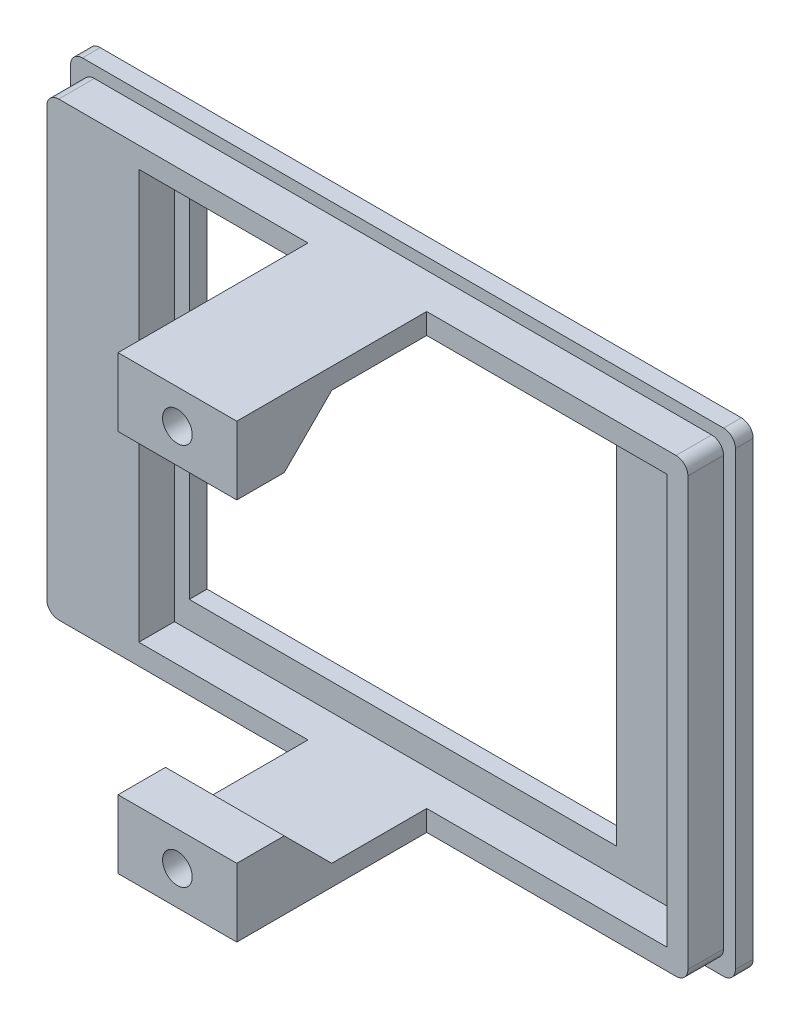
SolidWorks part; units mm, degrees
ref_plane "Front Plane" through (0, 0, 0) normal (0, 0, 1) x (1, 0, 0)
ref_plane "Top Plane" through (0, 0, 0) normal (0, 1, 0) x (1, 0, 0)
ref_plane "Right Plane" through (0, 0, 0) normal (1, 0, 0) x (0, 0, -1)
sketch "Sketch1" plane through (0, 0, 0) normal (0, 0, 1) x (1, 0, 0)
  line L1 (28, -20) -> (-28, -20)
  line L2 (28, -20) -> (28, 20)
  line L3 (28, 20) -> (-28, 20)
  line L4 (-28, -20) -> (-28, 20)
  line L5 (28, -20) -> (-28, 20) construction
  line L6 (28, 20) -> (-28, -20) construction
  line L7 (18, -15) -> (-18, -15)
  line L8 (18, -15) -> (18, 15)
  line L9 (18, 15) -> (-18, 15)
  line L10 (-18, -15) -> (-18, 15)
  line L11 (18, -15) -> (-18, 15) construction
  line L12 (18, 15) -> (-18, -15) construction
  point P0 (0, 0)
  point P6 (0, 0)
  dimension "D1" = 40
  dimension "D2" = 56
  dimension "D3" = 30
  dimension "D4" = 36
extrude "Boss-Extrude1" add sketch "Sketch1" along normal blind 1.5
sketch "Sketch2" plane through (0, 0, 1.5) normal (0, 0, 1) x (1, 0, 0)
  line L0 (28, 20) -> (-28, 20) construction
  line L1 (25.25, -17.25) -> (-19.25, -17.25)
  line L2 (25.25, -17.25) -> (25.25, 17.25)
  line L3 (25.25, 17.25) -> (-19.25, 17.25)
  line L4 (-19.25, -17.25) -> (-19.25, 17.25)
  line L5 (25.25, -17.25) -> (-19.25, 17.25) construction
  line L6 (25.25, 17.25) -> (-19.25, -17.25) construction
  line L7 (27, -19) -> (-27, -19)
  line L8 (27, -19) -> (27, 19)
  line L9 (27, 19) -> (-27, 19)
  line L10 (-27, -19) -> (-27, 19)
  line L11 (27, -19) -> (-27, 19) construction
  line L12 (27, 19) -> (-27, -19) construction
  line L13 (-28, 20) -> (-28, -20) construction
  point P0 (3, 0)
  point P5 (0, 0)
  point P15 (0, 0)
  dimension "D1" = 1
  dimension "D2" = 1
  dimension "D3" = 34.5
  dimension "D4" = 44.5
  dimension "D5" = 3
  dimension "D6" = 7.75
  dimension "D7" = 1.75
extrude "Boss-Extrude2" add sketch "Sketch2" along normal blind 3
sketch "Sketch3" plane through (0, 0, 4.5) normal (0, 0, 1) x (1, 0, 0)
  line L1 (27, 19) -> (-27, 19) construction
  line L2 (-5, 19) -> (5, 19)
  line L3 (-5, 19) -> (-5, 17.25)
  line L4 (-5, 17.25) -> (5, 17.25)
  line L5 (5, 19) -> (5, 17.25)
  line L6 (25.25, 17.25) -> (-19.25, 17.25) construction
  line L7 (-19.25, -17.25) -> (25.25, -17.25) construction
  line L8 (-5, -17.25) -> (5, -17.25)
  line L9 (-5, -17.25) -> (-5, -19)
  line L10 (-5, -19) -> (5, -19)
  line L11 (5, -17.25) -> (5, -19)
  line L12 (-27, -19) -> (27, -19) construction
  point P16 (0, 17.25)
  dimension "D1" = 10
extrude "Boss-Extrude3" add sketch "Sketch3" along normal blind 16
sketch "Sketch4" plane through (0, 17.25, 0) normal (0, -1, 0) x (-1, 0, 0)
  line L0 (5, -20.5) -> (-5, -20.5) construction
  line L1 (5, -20.5) -> (-5, -20.5)
  line L2 (5, -20.5) -> (5, -16.5)
  line L3 (5, -16.5) -> (-5, -16.5)
  line L4 (-5, -20.5) -> (-5, -16.5)
  line L5 (-5, -20.5) -> (-5, -4.5) construction
  line L6 (5, -20.5) -> (5, -4.5) construction
  line L7 (5, -20.5) -> (-5, -20.5) construction
  point P8 (5, -16.5)
  dimension "D1" = 4
extrude "Boss-Extrude4" add sketch "Sketch4" along normal blind 4
sketch "Sketch6" plane through (0, -17.25, 0) normal (0, 1, 0) x (1, 0, 0)
  line L0 (5, -20.5) -> (5, -4.5) construction
  line L1 (-5, -20.5) -> (5, -20.5)
  line L2 (-5, -20.5) -> (-5, -16.5)
  line L3 (-5, -16.5) -> (5, -16.5)
  line L4 (5, -20.5) -> (5, -16.5)
  dimension "D1" = 4
extrude "Boss-Extrude5" add sketch "Sketch6" along normal blind 4
chamfer "Chamfer1" distance 4 angle 45 2 edges at (0, -17.25, 16.5) (0, 17.25, 16.5)
sketch "Sketch7" plane through (0, 0, 20.5) normal (0, 0, 1) x (1, 0, 0)
  line L1 (0, 19) -> (0, 13.25) construction
  line L2 (27, 19) -> (-27, 19) construction
  line L3 (5, 13.25) -> (-5, 13.25) construction
  line L4 (0, -13.25) -> (0, -19) construction
  line L8 (-5, -13.25) -> (-5, -19)
  line L9 (-5, -19) -> (5, -19)
  line L10 (5, -19) -> (5, -13.25)
  line L11 (5, -13.25) -> (-5, -13.25)
  line L12 (-5, -13.25) -> (-5, -19) construction
  line L13 (-5, -19) -> (5, -19) construction
  line L14 (5, -19) -> (5, -13.25) construction
  line L15 (5, -13.25) -> (-5, -13.25) construction
  circle A0 centre (0, 16.125) radius 1.25
  circle A1 centre (0, -16.125) radius 1.25
  dimension "D1" = 2.5
  dimension "D2" = 0
extrude "Cut-Extrude2" cut sketch "Sketch7" against normal blind 6
fillet "Fillet1" radius 1 8 edges at (-27, -19, 3) (-27, 19, 3) (27, -19, 3) (27, 19, 3) (-28, -20, 0.75) (28, -20, 0.75) (28, 20, 0.75) (-28, 20, 0.75)
